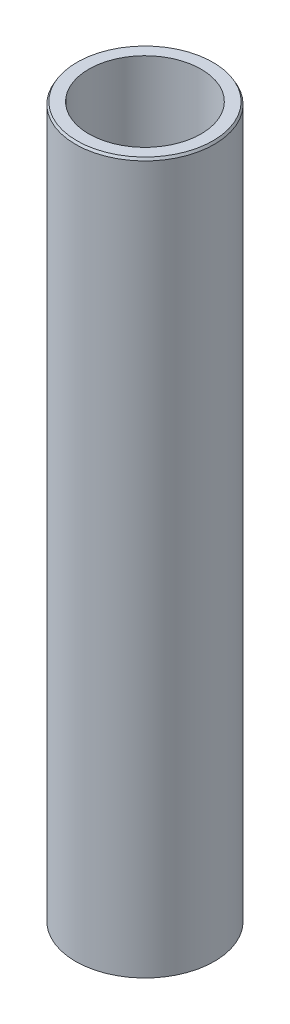
SolidWorks part; units mm, degrees
ref_plane "Front Plane" through (0, 0, 0) normal (0, 0, 1) x (1, 0, 0)
ref_plane "Top Plane" through (0, 0, 0) normal (0, 1, 0) x (1, 0, 0)
ref_plane "Right Plane" through (0, 0, 0) normal (1, 0, 0) x (0, 0, -1)
sketch "Sketch1" plane through (0, 0, 0) normal (0, 1, 0) x (1, 0, 0)
  circle A0 centre (0, 0) radius 57.5
  dimension "SHAFT_OD" = 115
extrude "Boss-Extrude1" add sketch "Sketch1" along normal blind 589.3689
sketch "Sketch2" plane through (0, 0, 0) normal (0, 1, 0) x (1, 0, 0)
  circle A0 centre (0, 0) radius 46.5204
  dimension "BORE_D" = 93.0409
extrude "Cut-Extrude1" cut sketch "Sketch2" along normal through all
chamfer "Chamfer1" distance 1.9883 angle 30 2 edges at (0, 589.3689, 57.5) (0, 0, 57.5) first distance on face at (0, 589.3689, 57.5) first distance on face at (0, 0, 46.5204)
